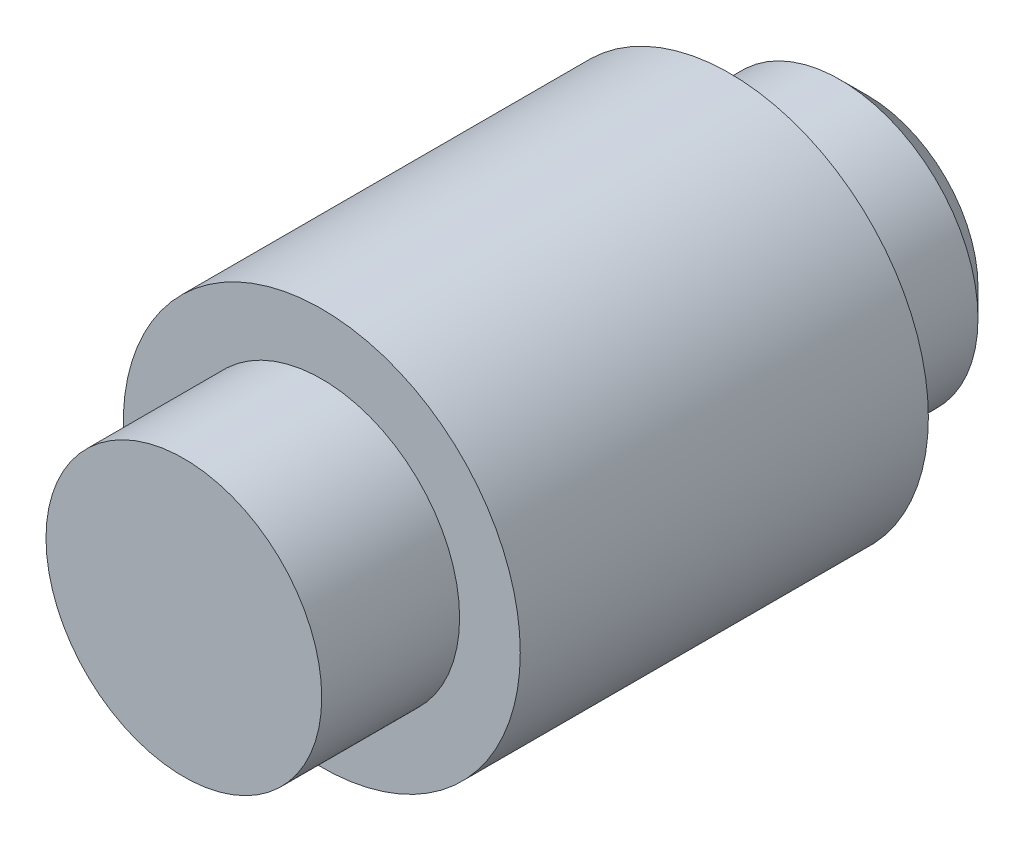
SolidWorks part; units mm, degrees
ref_plane "Front Plane" through (0, 0, 0) normal (0, 0, 1) x (1, 0, 0)
ref_plane "Top Plane" through (0, 0, 0) normal (0, 1, 0) x (1, 0, 0)
ref_plane "Right Plane" through (0, 0, 0) normal (1, 0, 0) x (0, 0, -1)
sketch "Sketch2" plane through (0, 0, 0) normal (0, 0, 1) x (1, 0, 0)
  circle A0 centre (0, 0) radius 1.25
  dimension "D1" = 2.5
sketch "Sketch3" plane through (0, 0, 0) normal (0, 0, 1) x (1, 0, 0)
  line L5 (-3.6, 3.6) -> (3.6, 3.6) construction
  line L6 (-3.6, 3.6) -> (-3.6, -3.6) construction
  line L7 (-3.6, -3.6) -> (3.6, -3.6) construction
  line L8 (3.6, 3.6) -> (3.6, -3.6) construction
  circle A0 centre (0, 0) radius 3.6
  point P4 (0, 3.6)
  point P6 (-3.6, 0)
  dimension "D1" = 7.2
extrude "Boss-Extrude1" add sketch "Sketch3" along normal blind 7.4
sketch "Sketch4" plane through (0, 0, 0) normal (0, 0, 1) x (1, 0, 0)
  circle A0 centre (0, 0) radius 2.5
  dimension "D1" = 5
extrude "Boss-Extrude2" add sketch "Sketch4" against normal blind 2.5
sketch "Sketch5" plane through (0, 0, 7.4) normal (0, 0, 1) x (1, 0, 0)
  circle A0 centre (0, 0) radius 2.5
  dimension "D1" = 5
extrude "Boss-Extrude3" add sketch "Sketch5" along normal blind 2.5
chamfer "Chamfer1" distance 0.5 angle 45 1 edges at (2.5, 0, -2.5)
equation "\"length\"=7.4"
equation "\"D1@Boss-Extrude1\"=\"length\""
equation "\"hole\"=5"
equation "\"D1@Sketch5\"=\"hole\""
equation "\"D1@Sketch4\"=\"hole\""
